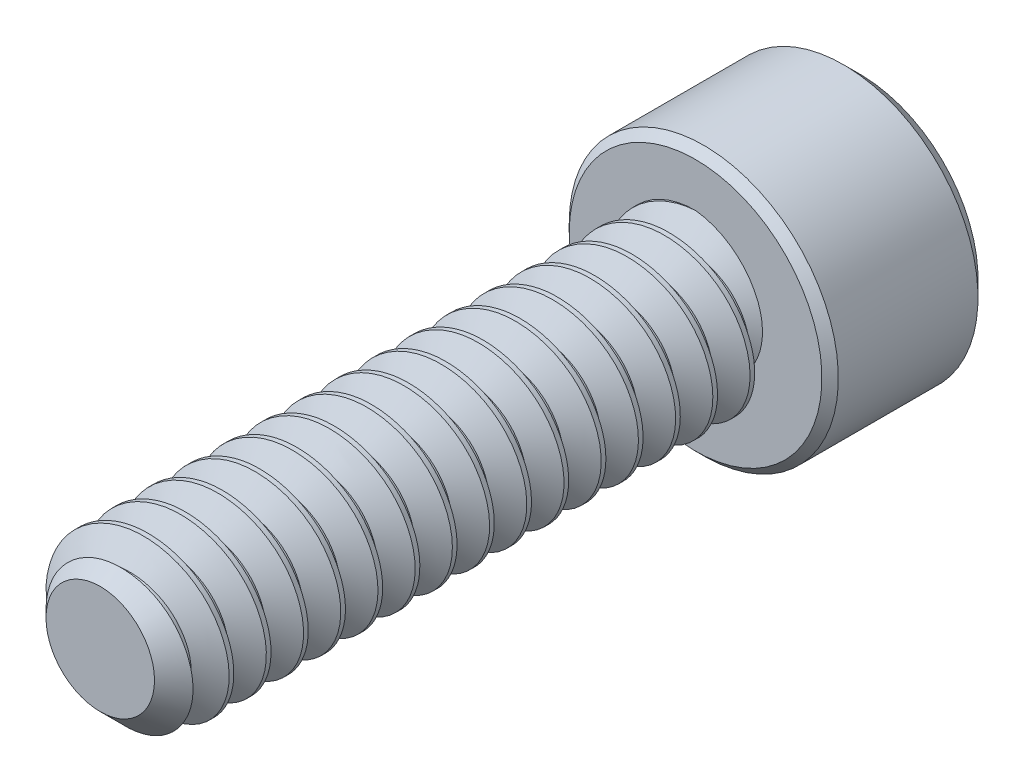
SolidWorks part; units mm, degrees
ref_plane "Front Plane" through (0, 0, 0) normal (0, 0, 1) x (1, 0, 0)
ref_plane "Top Plane" through (0, 0, 0) normal (0, 1, 0) x (1, 0, 0)
ref_plane "Right Plane" through (0, 0, 0) normal (1, 0, 0) x (0, 0, -1)
sketch "Sketch1" plane through (0, 0, 0) normal (0, 0, 1) x (1, 0, 0)
  line L0 (0, 1.7526) -> (0, -1.7526) construction
  circle A0 centre (0, 0) radius 1.7526
  dimension "OD" = 3.5052
extrude "Extrude1" add sketch "Sketch1" against normal blind 12.7
sketch "Sketch2" plane through (0, 0, 0) normal (0, 0, 1) x (1, 0, 0)
  circle A0 centre (0, 0) radius 1.7526 construction
  circle A1 centre (0, 0) radius 1.7526
curve "Helix/Spiral1" pitch 0.7937 height 13.4937 turns 17 parameters "pitch"=0.7937
chamfer "Chamfer3" distance 0.5953 angle 45 1 edges at (1.7526, 0, 0)
sketch "Sketch3" plane through (0, 0, 0) normal (1, 0, 0) x (0, 0, -1)
  line L0 (-0.6945, 1.7526) -> (-0.3969, 1.237)
  line L1 (-0.3969, 1.237) -> (-0.2977, 1.237)
  line L2 (-0.2977, 1.237) -> (0, 1.7526)
  line L3 (-0.6945, 1.7526) -> (0, 1.7526)
  line L4 (-0.3473, 1.7526) -> (-0.3473, 1.237) construction
  line L5 (-0.5457, 1.4948) -> (-0.1488, 1.4948) construction
  line L6 (0, 1.7526) -> (0, -1.7526) construction
  dimension "D1" = 0.0992
  dimension "D2" = 0.3969
  dimension "D3" = 60
sweep "Cut-Sweep1" cut profiles "Sketch3" path "Helix/Spiral1"
sketch "Sketch6" plane through (0, 0, -12.7) normal (0, 0, -1) x (-1, 0, 0)
  circle A0 centre (0, 0) radius 2.8702
  dimension "head dia" = 5.7404
extrude "Extrude2" add sketch "Sketch6" along normal blind 3.5052
sketch "Sketch7" plane through (0, 0, -16.2052) normal (0, 0, -1) x (-1, 0, 0)
  line L1 (0, 1.604) -> (-1.3891, 0.802)
  line L2 (-1.3891, 0.802) -> (-1.3891, -0.802)
  line L3 (-1.3891, -0.802) -> (0, -1.604)
  line L4 (0, -1.604) -> (1.3891, -0.802)
  line L5 (1.3891, -0.802) -> (1.3891, 0.802)
  line L6 (1.3891, 0.802) -> (0, 1.604)
  circle A0 centre (0, 0) radius 1.3891 construction
  dimension "hex dia" = 2.7781
extrude "Cut-Extrude1" cut sketch "Sketch7" against normal blind 2.0836
sketch "Sketch8" plane through (0, 0, -16.2052) normal (0, 0, -1) x (-1, 0, 0)
  circle A0 centre (0, 0) radius 1.604
extrude "Cut-Extrude2" cut sketch "Sketch8" against normal blind 0.3505 draft 45
chamfer "Chamfer1" distance 0.3505 angle 45 1 edges at (-2.8702, 0, -16.2052)
chamfer "Chamfer2" distance 0.1753 angle 45 1 edges at (-2.8702, 0, -12.7)
sketch "Sketch9" plane through (0, 0, 0) normal (1, 0, 0) x (0, 0, -1)
  line L0 (0, 1.7526) -> (0, -1.7526) construction
  line L1 (4.3656, 1.7526) -> (4.3656, -1.7526) construction
  line L2 (12.7, 2.8702) -> (12.7, -2.8702) construction
  line L3 (16.2052, 2.8702) -> (16.2052, -2.8702) construction
  line L4 (16.2052, 0) -> (0, 0) construction
  dimension "D1" = 4.3656
  dimension "D2" = 3.5052
  dimension "D3" = 5.7404
  dimension "D4" = 12.7
equation "\"D3@Helix/Spiral1\" = \"screw length@Extrude1\"+\"pitch@Helix/Spiral1\""
equation "\"D1@Sketch3\" = \"pitch@Helix/Spiral1\"*.125"
equation "\"D2@Sketch3\" = \"pitch@Helix/Spiral1\"*.5"
equation "\"D1@Cut-Extrude1\" = \"hex dia@Sketch7\"*.75"
equation "\"D1@Chamfer1\" = \"head depth@Extrude2\"/10"
equation "\"D1@Sketch9\" = \"pitch@Helix/Spiral1\"*5.5"
equation "\"D1@Chamfer2\" = \"D1@Chamfer1\"/2"
equation "\"D1@Cut-Extrude2\" = \"D1@Chamfer2\"*2"
equation "\"D1@Chamfer3\" = \"pitch@Helix/Spiral1\"*.750"
equation "\"D2@Sketch9\" = \"head depth@Extrude2\""
equation "\"D3@Sketch9\" = \"head dia@Sketch6\""
equation "\"D4@Sketch9\" = \"screw length@Extrude1\""
